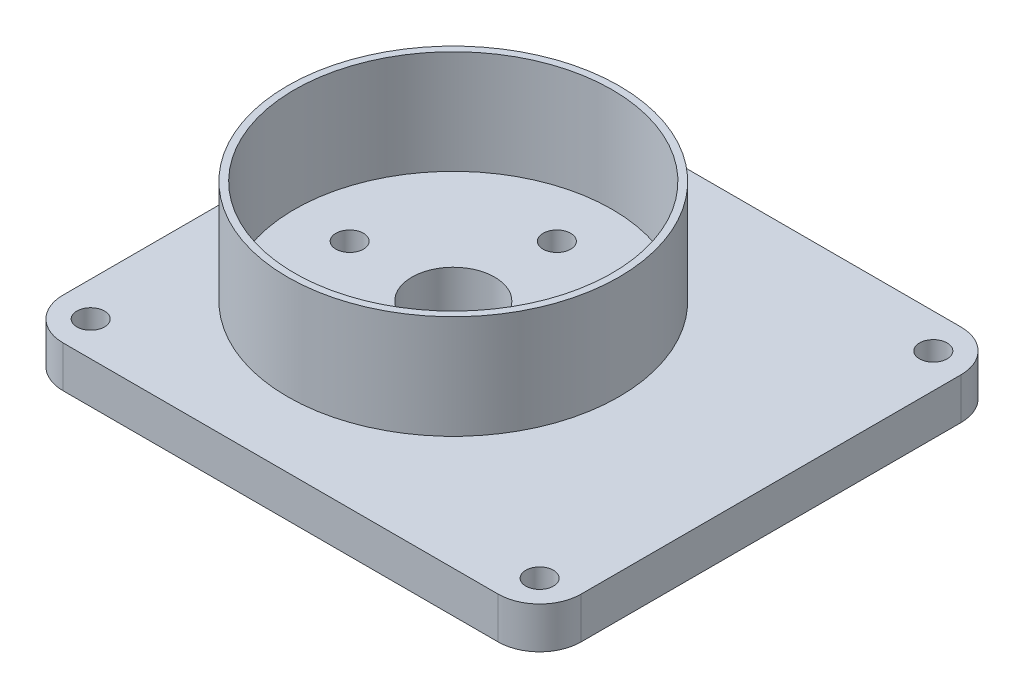
SolidWorks part; units mm, degrees
ref_plane "前视基准面" through (0, 0, 0) normal (0, 0, 1) x (1, 0, 0)
ref_plane "上视基准面" through (0, 0, 0) normal (0, 1, 0) x (1, 0, 0)
ref_plane "右视基准面" through (0, 0, 0) normal (1, 0, 0) x (0, 0, -1)
sketch "草图1" plane through (0, 0, 0) normal (0, 1, 0) x (1, 0, 0)
  line L0 (-18.75, 0) -> (18.75, 0) construction
  line L1 (-18.75, 16.75) -> (18.75, 16.75)
  line L2 (-18.75, 16.75) -> (-18.75, -16.75)
  line L3 (-18.75, -16.75) -> (18.75, -16.75)
  line L4 (18.75, 16.75) -> (18.75, -16.75)
  line L5 (-18.75, 16.75) -> (18.75, -16.75) construction
  line L6 (-18.75, -16.75) -> (18.75, 16.75) construction
  circle A0 centre (-4.25, 0) radius 12
  circle A1 centre (-4.25, 0) radius 3
  circle A2 centre (-4.25, 0) radius 11.5
  circle A3 centre (-11.75, 0) radius 1
  circle A4 centre (-4.25, 7.5) radius 1
  circle A5 centre (3.25, 0) radius 1
  circle A6 centre (-4.25, -7.5) radius 1
  circle A7 centre (-16.25, 14.25) radius 1
  circle A8 centre (-16.25, -14.25) radius 1
  circle A9 centre (16.25, 14.25) radius 1
  circle A10 centre (16.25, -14.25) radius 1
  point P0 (0, 0)
  point P23 (-4.25, 0)
  point P32 (0, 0)
  dimension "D3" = 24
  dimension "D5" = 6
  dimension "D7" = 2
  dimension "D10" = 2
  dimension "D1" = 33.5
  dimension "D2" = 37.5
  dimension "D4" = 0.5
  dimension "D6" = 14.5
  dimension "D8" = 7.5
  dimension "D11" = 2.5
  dimension "D12" = 2.5
  dimension "D9" = 4
  dimension "D13" = 2
extrude "凸台-拉伸1" add sketch "草图1" along normal blind 3 contours L3 L4 L1 L2 | A8 | A10 | A9 | A7 | A4 | A3 | A6 | A5 | A1
extrude "凸台-拉伸2" add sketch "草图1<3>" along normal blind 10.5 contours A0 | A2
sketch "草图1<3>" plane through (0, 0, 0) normal (0, 1, 0) x (1, 0, 0) same geometry as "草图1"
fillet "圆角1" radius 3 4 edges at (-18.75, 1.5, 16.75) (18.75, 1.5, 16.75) (18.75, 1.5, -16.75) (-18.75, 1.5, -16.75)
equation "\"D12@草图1\"= \"D11@草图1\""
